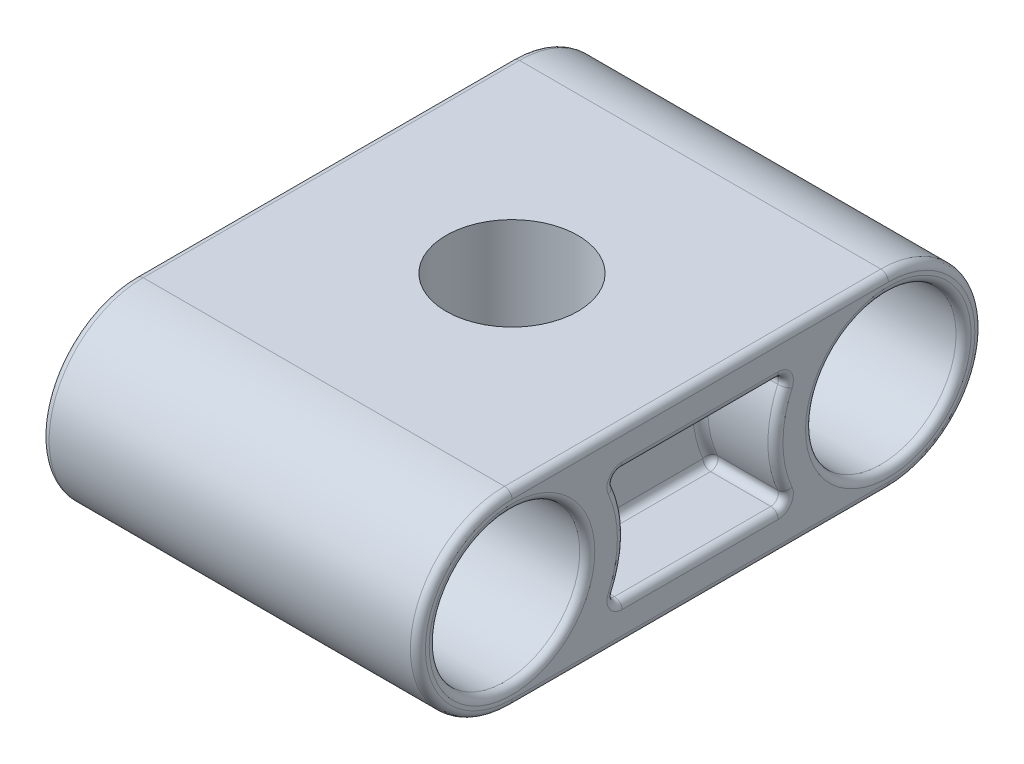
SolidWorks part; units mm, degrees
ref_plane "Front Plane" through (0, 0, 0) normal (0, 0, 1) x (1, 0, 0)
ref_plane "Top Plane" through (0, 0, 0) normal (0, 1, 0) x (1, 0, 0)
ref_plane "Right Plane" through (0, 0, 0) normal (1, 0, 0) x (0, 0, -1)
sketch "Sketch1" plane through (0, 0, 0) normal (1, 0, 0) x (0, 0, -1)
  line L0 (-50, 0) -> (50, 0) construction
  line L1 (-50, 25) -> (50, 25)
  line L2 (-50, -25) -> (50, -25)
  line L3 (-24.0192, 15) -> (24.0192, 15)
  line L4 (-24.0192, -15) -> (24.0192, -15)
  arc A0 (-50, 25) -> (-50, -25) centre (-50, 0) ccw
  arc A1 (50, -25) -> (50, 25) centre (50, 0) ccw
  circle A2 centre (-50, 0) radius 20
  circle A3 centre (50, 0) radius 20
  arc A4 (-24.0192, 15) -> (-24.0192, -15) centre (-50, 0) cw
  arc A5 (24.0192, 15) -> (24.0192, -15) centre (50, 0) ccw
  point P3 (0, 0)
  point P18 (0, 0)
  point P19 (0, 0)
  point P20 (-70, 15)
  point P21 (0, 0)
  dimension "D1" = 150
  dimension "D3" = 40
  dimension "D4" = 30
  dimension "D2" = 50
  dimension "D5" = 10
  dimension "D6" = 10
extrude "Boss-Extrude1" add sketch "Sketch1" along normal blind 100 contours A4 L0 A5 L3 | L0 A4 L4 A5 | L2 A1 L1 A0 A2 A4 L3 A5 A3 L4 region at (0, 7.7323, 0) region at (0, -7.7323, 0) region at (0, 23.4189, 0)
extrude "Cut-Extrude1" cut sketch "Sketch1<3>" along normal blind 20 contours A4 L0 A5 L3 | L0 A4 L4 A5 region at (0, 7.7323, 0) region at (0, -7.7323, 0)
sketch "Sketch1<3>" plane through (0, 0, 0) normal (1, 0, 0) x (0, 0, -1) same geometry as "Sketch1"
extrude "Cut-Extrude2" cut sketch "Sketch1<4>" against normal blind 20 from surface contours A4 L0 A5 L3 | L0 A4 L4 A5 region at (0, 7.7323, 0) region at (0, -7.7323, 0) starting at face at (100, 0, -70)
sketch "Sketch1<4>" plane through (0, 0, 0) normal (1, 0, 0) x (0, 0, -1) same geometry as "Sketch1"
sketch "Sketch2" plane through (0, 25, 0) normal (0, 1, 0) x (1, 0, 0)
  line L0 (100, 50) -> (0, 50) construction
  line L1 (100, -50) -> (100, 50) construction
  circle A0 centre (50, 0) radius 17.5
  dimension "D3" = 35
  dimension "D1" = 50
  dimension "D2" = 50
extrude "Cut-Extrude3" cut sketch "Sketch2" against normal through all
fillet "Fillet1" radius 2 36 edges at (0, 15, 0) (0, -15, 0) (0, 0, 75) (0, -25, 0) (0, 0, -75) (100, 0, 75) (100, -25, 0) (100, 0, -75) (100, -15, 0) (90, -15, 24.0192) (100, 0, 20) (90, 15, 24.0192) (100, 15, 0) (80, -15, 0) (80, 0, 20) (80, 15, 0) (90, -15, -24.0192) (80, 0, -20) (90, 15, -24.0192) (100, 0, -20) (10, -15, 24.0192) (10, 15, 24.0192) (0, 0, 20) (20, -15, 0) (20, 15, 0) (20, 0, 20) (10, 15, -24.0192) (20, 0, -20) (10, -15, -24.0192) (0, 0, -20) (100, 0, -70) (100, 0, 30) (0, 0, -70) (0, 0, 30) (0, 25, 0) (100, 25, 0)
